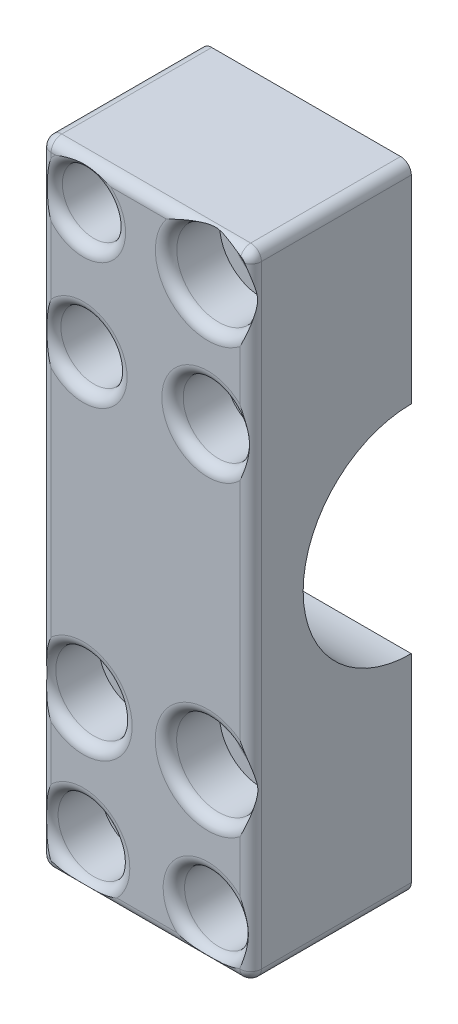
SolidWorks part; units mm, degrees
ref_plane "Front Plane" through (0, 0, 0) normal (1, 0, 0) x (0, 1, 0)
ref_plane "Top Plane" through (0, 0, 0) normal (0, 0, 1) x (0, 1, 0)
ref_plane "Right Plane" through (0, 0, 0) normal (0, 1, 0) x (-1, 0, 0)
sketch "Sketch1" plane through (0, 0, 0) normal (0, 0, 1) x (0, 1, 0)
  line L0 (-29.615, 9.82) -> (29.615, 9.82)
  line L7 (29.615, 9.82) -> (29.615, -9.82)
  line L8 (-29.615, -9.82) -> (29.615, -9.82)
  line L9 (-29.615, 9.82) -> (-29.615, -9.82)
  circle A0 centre (-25.615, 5.82) radius 1.6
  circle A1 centre (25.615, 5.82) radius 1.6
  circle A2 centre (25.615, -5.82) radius 1.6
  circle A3 centre (-25.615, -5.82) radius 1.6
  circle A4 centre (-14.015, 5.82) radius 1.6
  circle A5 centre (-14.015, -5.82) radius 1.6
  circle A6 centre (13.975, -5.82) radius 1.6
  circle A7 centre (13.975, 5.82) radius 1.6
  point P0 (0, 0)
  dimension "D6" = 3.2
  dimension "D1" = 51.23
  dimension "D2" = 11.64
extrude "Boss-Extrude1" add sketch "Sketch1" along normal blind 15
sketch "Sketch2" plane through (0, 0, 15) normal (0, 0, 1) x (1, 0, 0)
  circle A0 centre (-5.82, 25.615) radius 2.9526
  circle A1 centre (5.82, 25.615) radius 3.9034
  circle A2 centre (-5.82, 13.975) radius 3.0921
  circle A3 centre (5.82, 13.975) radius 3.2998
  circle A4 centre (-5.82, -14.015) radius 3.5676
  circle A5 centre (-5.82, -25.615) radius 3.3479
  circle A6 centre (5.82, -25.615) radius 3.1768
  circle A7 centre (5.82, -14.015) radius 3.916
extrude "Cut-Extrude1" cut sketch "Sketch2" against normal blind 5
sketch "Sketch4" plane through (0, 0, 0) normal (0, 0, -1) x (1, 0, 0)
  line L0 (-5.82, 14.015) -> (5.82, 14.015) construction
  line L2 (-5.82, 25.615) -> (5.82, 25.615) construction
  line L3 (-14.6617, 10.035) -> (17.8153, 10.035) construction
  line L4 (-5.82, -25.615) -> (5.82, -25.615) construction
  line L5 (-14.0453, -9.995) -> (15.6977, -9.995) construction
  dimension "D1" = 15.58
  dimension "D2" = 15.62
sketch "Sketch6" plane through (9.82, 0, 0) normal (1, 0, 0) x (0, 1, 0)
  line L0 (-29.615, 0) -> (29.615, 0) construction
  circle A0 centre (0, 0) radius 10.1
  dimension "D1" = 20.2
extrude "Cut-Extrude2" cut sketch "Sketch6" against normal through all
fillet "Fillet1" radius 1 24 edges at (8.9968, -25.615, 15) (-2.4721, -25.615, 15) (9.736, -14.015, 15) (-2.2524, -14.015, 15) (-2.7279, 13.975, 15) (-2.8674, 25.615, 15) (9.7234, 25.615, 15) (9.1198, 13.975, 15) (-4.22, -25.615, 10) (7.42, -25.615, 10) (-4.22, -14.015, 10) (7.42, -14.015, 10) (7.42, 13.975, 10) (-4.22, 25.615, 10) (7.42, 25.615, 10) (-4.22, 13.975, 10) (9.82, 29.615, 7.5) (9.82, -29.615, 7.5) (-9.82, -29.615, 7.5) (-9.82, 29.615, 7.5) (0, 29.615, 15) (9.82, 0, 15) (-9.82, 0, 15) (0, -29.615, 15)
